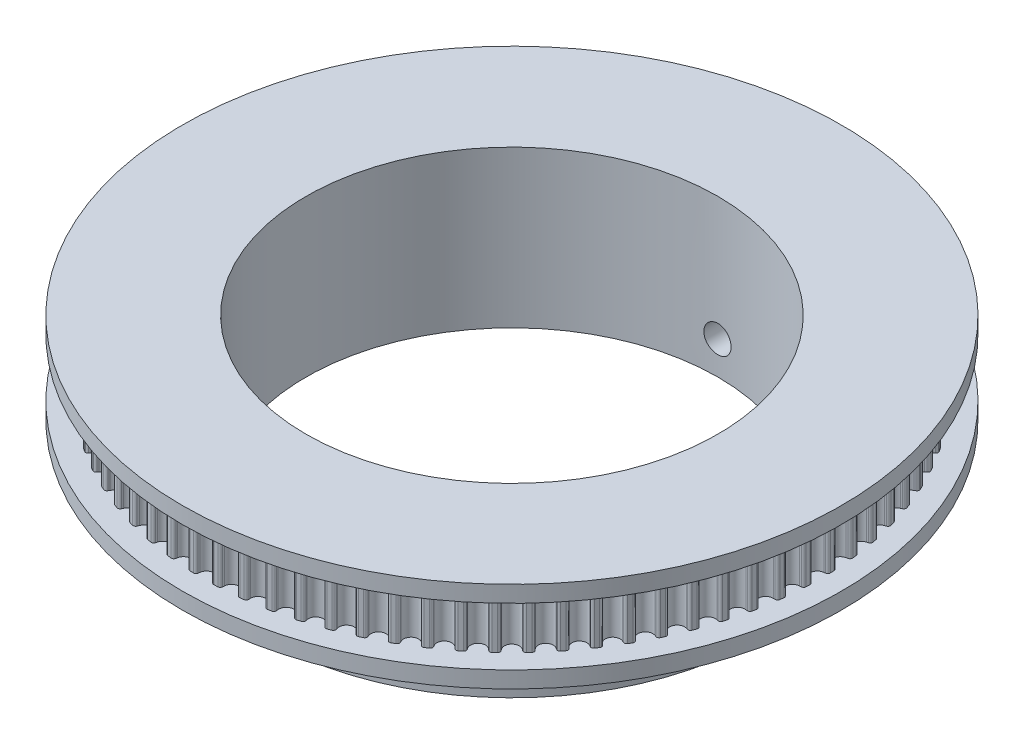
SolidWorks part; units mm, degrees
material "6061 合金"
ref_plane "前视基准面" through (0, 0, 0) normal (0, 0, 1) x (1, 0, 0)
ref_plane "上视基准面" through (0, 0, 0) normal (0, 1, 0) x (1, 0, 0)
ref_plane "右视基准面" through (0, 0, 0) normal (1, 0, 0) x (0, 0, -1)
sketch "草图1" plane through (0, 0, 0) normal (0, 1, 0) x (1, 0, 0)
  circle A0 centre (0, 0) radius 40
  dimension "D1" = 80
extrude "凸台-拉伸1" add sketch "草图1" along normal mid plane 11
sketch "草图2" plane through (0, 0, 0) normal (0, 1, 0) x (1, 0, 0)
  line L0 (0, 0) -> (0, 37.815) construction
  line L1 (-0.9274, 37.1503) -> (-0.9032, 36.9531)
  line L2 (0.9274, 37.1503) -> (0.9032, 36.9531)
  line L3 (-0.95, 37.2332) -> (0.95, 37.2332) construction
  line L4 (1.9902, 37.1086) -> (1.9989, 36.9101)
  line L5 (3.8394, 36.9631) -> (3.7997, 36.7683)
  line L6 (4.8956, 36.838) -> (4.8886, 36.6394)
  line L7 (6.7276, 36.5479) -> (6.6728, 36.3569)
  line L8 (7.7708, 36.3404) -> (7.7483, 36.1429)
  line L9 (9.5744, 35.9074) -> (9.5048, 35.7212)
  line L10 (10.598, 35.6187) -> (10.5601, 35.4236)
  line L11 (12.3621, 35.0455) -> (12.2781, 34.8654)
  line L12 (13.36, 34.6774) -> (13.3069, 34.4859)
  line L13 (15.0737, 33.9675) -> (14.9758, 33.7946)
  line L14 (16.0396, 33.5222) -> (15.9716, 33.3355)
  line L15 (17.6923, 32.6802) -> (17.5811, 32.5154)
  line L16 (18.6202, 32.1605) -> (18.5378, 31.9796)
  line L17 (20.2018, 31.1913) -> (20.0781, 31.0358)
  line L18 (21.0861, 30.6004) -> (20.9898, 30.4266)
  line L19 (22.5867, 29.5101) -> (22.4512, 29.3648)
  line L20 (23.422, 28.8517) -> (23.3123, 28.6859)
  line L21 (24.8324, 27.647) -> (24.6859, 27.5128)
  line L22 (25.6135, 26.9251) -> (25.4911, 26.7685)
  line L23 (26.9251, 25.6135) -> (26.7685, 25.4911)
  line L24 (27.647, 24.8324) -> (27.5128, 24.6859)
  line L25 (28.8517, 23.422) -> (28.6859, 23.3123)
  line L26 (29.5101, 22.5867) -> (29.3648, 22.4512)
  line L27 (30.6004, 21.0861) -> (30.4266, 20.9898)
  line L28 (31.1913, 20.2018) -> (31.0358, 20.0781)
  line L29 (32.1605, 18.6202) -> (31.9796, 18.5378)
  line L30 (32.6802, 17.6923) -> (32.5154, 17.5811)
  line L31 (33.5222, 16.0396) -> (33.3355, 15.9716)
  line L32 (33.9675, 15.0737) -> (33.7946, 14.9758)
  line L33 (34.6774, 13.36) -> (34.4859, 13.3069)
  line L34 (35.0455, 12.3621) -> (34.8654, 12.2781)
  line L35 (35.6187, 10.598) -> (35.4236, 10.5601)
  line L36 (35.9074, 9.5744) -> (35.7212, 9.5048)
  line L37 (36.3404, 7.7708) -> (36.1429, 7.7483)
  line L38 (36.5479, 6.7276) -> (36.3569, 6.6728)
  line L39 (36.838, 4.8956) -> (36.6394, 4.8886)
  line L40 (36.9631, 3.8394) -> (36.7683, 3.7997)
  line L41 (37.1086, 1.9902) -> (36.9101, 1.9989)
  line L42 (37.1503, 0.9274) -> (36.9531, 0.9032)
  line L43 (37.1503, -0.9274) -> (36.9531, -0.9032)
  line L44 (37.1086, -1.9902) -> (36.9101, -1.9989)
  line L45 (36.9631, -3.8394) -> (36.7683, -3.7997)
  line L46 (36.838, -4.8956) -> (36.6394, -4.8886)
  line L47 (36.5479, -6.7276) -> (36.3569, -6.6728)
  line L48 (36.3404, -7.7708) -> (36.1429, -7.7483)
  line L49 (35.9074, -9.5744) -> (35.7212, -9.5048)
  line L50 (35.6187, -10.598) -> (35.4236, -10.5601)
  line L51 (35.0455, -12.3621) -> (34.8654, -12.2781)
  line L52 (34.6774, -13.36) -> (34.4859, -13.3069)
  line L53 (33.9675, -15.0737) -> (33.7946, -14.9758)
  line L54 (33.5222, -16.0396) -> (33.3355, -15.9716)
  line L55 (32.6802, -17.6923) -> (32.5154, -17.5811)
  line L56 (32.1605, -18.6202) -> (31.9796, -18.5378)
  line L57 (31.1913, -20.2018) -> (31.0358, -20.0781)
  line L58 (30.6004, -21.0861) -> (30.4266, -20.9898)
  line L59 (29.5101, -22.5867) -> (29.3648, -22.4512)
  line L60 (28.8517, -23.422) -> (28.6859, -23.3123)
  line L61 (27.647, -24.8324) -> (27.5128, -24.6859)
  line L62 (26.9251, -25.6135) -> (26.7685, -25.4911)
  line L63 (25.6135, -26.9251) -> (25.4911, -26.7685)
  line L64 (24.8324, -27.647) -> (24.6859, -27.5128)
  line L65 (23.422, -28.8517) -> (23.3123, -28.6859)
  line L66 (22.5867, -29.5101) -> (22.4512, -29.3648)
  line L67 (21.0861, -30.6004) -> (20.9898, -30.4266)
  line L68 (20.2018, -31.1913) -> (20.0781, -31.0358)
  line L69 (18.6202, -32.1605) -> (18.5378, -31.9796)
  line L70 (17.6923, -32.6802) -> (17.5811, -32.5154)
  line L71 (16.0396, -33.5222) -> (15.9716, -33.3355)
  line L72 (15.0737, -33.9675) -> (14.9758, -33.7946)
  line L73 (13.36, -34.6774) -> (13.3069, -34.4859)
  line L74 (12.3621, -35.0455) -> (12.2781, -34.8654)
  line L75 (10.598, -35.6187) -> (10.5601, -35.4236)
  line L76 (9.5744, -35.9074) -> (9.5048, -35.7212)
  line L77 (7.7708, -36.3404) -> (7.7483, -36.1429)
  line L78 (6.7276, -36.5479) -> (6.6728, -36.3569)
  line L79 (4.8956, -36.838) -> (4.8886, -36.6394)
  line L80 (3.8394, -36.9631) -> (3.7997, -36.7683)
  line L81 (1.9902, -37.1086) -> (1.9989, -36.9101)
  line L82 (0.9274, -37.1503) -> (0.9032, -36.9531)
  line L83 (-0.9274, -37.1503) -> (-0.9032, -36.9531)
  line L84 (-1.9902, -37.1086) -> (-1.9989, -36.9101)
  line L85 (-3.8394, -36.9631) -> (-3.7997, -36.7683)
  line L86 (-4.8956, -36.838) -> (-4.8886, -36.6394)
  line L87 (-6.7276, -36.5479) -> (-6.6728, -36.3569)
  line L88 (-7.7708, -36.3404) -> (-7.7483, -36.1429)
  line L89 (-9.5744, -35.9074) -> (-9.5048, -35.7212)
  line L90 (-10.598, -35.6187) -> (-10.5601, -35.4236)
  line L91 (-12.3621, -35.0455) -> (-12.2781, -34.8654)
  line L92 (-13.36, -34.6774) -> (-13.3069, -34.4859)
  line L93 (-15.0737, -33.9675) -> (-14.9758, -33.7946)
  line L94 (-16.0396, -33.5222) -> (-15.9716, -33.3355)
  line L95 (-17.6923, -32.6802) -> (-17.5811, -32.5154)
  line L96 (-18.6202, -32.1605) -> (-18.5378, -31.9796)
  line L97 (-20.2018, -31.1913) -> (-20.0781, -31.0358)
  line L98 (-21.0861, -30.6004) -> (-20.9898, -30.4266)
  line L99 (-22.5867, -29.5101) -> (-22.4512, -29.3648)
  line L100 (-23.422, -28.8517) -> (-23.3123, -28.6859)
  line L101 (-24.8324, -27.647) -> (-24.6859, -27.5128)
  line L102 (-25.6135, -26.9251) -> (-25.4911, -26.7685)
  line L103 (-26.9251, -25.6135) -> (-26.7685, -25.4911)
  line L104 (-27.647, -24.8324) -> (-27.5128, -24.6859)
  line L105 (-28.8517, -23.422) -> (-28.6859, -23.3123)
  line L106 (-29.5101, -22.5867) -> (-29.3648, -22.4512)
  line L107 (-30.6004, -21.0861) -> (-30.4266, -20.9898)
  line L108 (-31.1913, -20.2018) -> (-31.0358, -20.0781)
  line L109 (-32.1605, -18.6202) -> (-31.9796, -18.5378)
  line L110 (-32.6802, -17.6923) -> (-32.5154, -17.5811)
  line L111 (-33.5222, -16.0396) -> (-33.3355, -15.9716)
  line L112 (-33.9675, -15.0737) -> (-33.7946, -14.9758)
  line L113 (-34.6774, -13.36) -> (-34.4859, -13.3069)
  line L114 (-35.0455, -12.3621) -> (-34.8654, -12.2781)
  line L115 (-35.6187, -10.598) -> (-35.4236, -10.5601)
  line L116 (-35.9074, -9.5744) -> (-35.7212, -9.5048)
  line L117 (-36.3404, -7.7708) -> (-36.1429, -7.7483)
  line L118 (-36.5479, -6.7276) -> (-36.3569, -6.6728)
  line L119 (-36.838, -4.8956) -> (-36.6394, -4.8886)
  line L120 (-36.9631, -3.8394) -> (-36.7683, -3.7997)
  line L121 (-37.1086, -1.9902) -> (-36.9101, -1.9989)
  line L122 (-37.1503, -0.9274) -> (-36.9531, -0.9032)
  line L123 (-37.1503, 0.9274) -> (-36.9531, 0.9032)
  line L124 (-37.1086, 1.9902) -> (-36.9101, 1.9989)
  line L125 (-36.9631, 3.8394) -> (-36.7683, 3.7997)
  line L126 (-36.838, 4.8956) -> (-36.6394, 4.8886)
  line L127 (-36.5479, 6.7276) -> (-36.3569, 6.6728)
  line L128 (-36.3404, 7.7708) -> (-36.1429, 7.7483)
  line L129 (-35.9074, 9.5744) -> (-35.7212, 9.5048)
  line L130 (-35.6187, 10.598) -> (-35.4236, 10.5601)
  line L131 (-35.0455, 12.3621) -> (-34.8654, 12.2781)
  line L132 (-34.6774, 13.36) -> (-34.4859, 13.3069)
  line L133 (-33.9675, 15.0737) -> (-33.7946, 14.9758)
  line L134 (-33.5222, 16.0396) -> (-33.3355, 15.9716)
  line L135 (-32.6802, 17.6923) -> (-32.5154, 17.5811)
  line L136 (-32.1605, 18.6202) -> (-31.9796, 18.5378)
  line L137 (-31.1913, 20.2018) -> (-31.0358, 20.0781)
  line L138 (-30.6004, 21.0861) -> (-30.4266, 20.9898)
  line L139 (-29.5101, 22.5867) -> (-29.3648, 22.4512)
  line L140 (-28.8517, 23.422) -> (-28.6859, 23.3123)
  line L141 (-27.647, 24.8324) -> (-27.5128, 24.6859)
  line L142 (-26.9251, 25.6135) -> (-26.7685, 25.4911)
  line L143 (-25.6135, 26.9251) -> (-25.4911, 26.7685)
  line L144 (-24.8324, 27.647) -> (-24.6859, 27.5128)
  line L145 (-23.422, 28.8517) -> (-23.3123, 28.6859)
  line L146 (-22.5867, 29.5101) -> (-22.4512, 29.3648)
  line L147 (-21.0861, 30.6004) -> (-20.9898, 30.4266)
  line L148 (-20.2018, 31.1913) -> (-20.0781, 31.0358)
  line L149 (-18.6202, 32.1605) -> (-18.5378, 31.9796)
  line L150 (-17.6923, 32.6802) -> (-17.5811, 32.5154)
  line L151 (-16.0396, 33.5222) -> (-15.9716, 33.3355)
  line L152 (-15.0737, 33.9675) -> (-14.9758, 33.7946)
  line L153 (-13.36, 34.6774) -> (-13.3069, 34.4859)
  line L154 (-12.3621, 35.0455) -> (-12.2781, 34.8654)
  line L155 (-10.598, 35.6187) -> (-10.5601, 35.4236)
  line L156 (-9.5744, 35.9074) -> (-9.5048, 35.7212)
  line L157 (-7.7708, 36.3404) -> (-7.7483, 36.1429)
  line L158 (-6.7276, 36.5479) -> (-6.6728, 36.3569)
  line L159 (-4.8956, 36.838) -> (-4.8886, 36.6394)
  line L160 (-3.8394, 36.9631) -> (-3.7997, 36.7683)
  line L161 (-1.9902, 37.1086) -> (-1.9989, 36.9101)
  arc A0 (-1.2351, 37.4136) -> (-1.7041, 37.3952) centre (0, 0) ccw
  arc A1 (1.7041, 37.3952) -> (1.2351, 37.4136) centre (0, 0) ccw
  arc A3 (-0.9032, 36.9531) -> (0.9032, 36.9531) centre (0, 37.064) ccw
  arc A4 (-0.9274, 37.1503) -> (-1.2351, 37.4136) centre (-1.2252, 37.1138) ccw
  arc A5 (0.9274, 37.1503) -> (1.2351, 37.4136) centre (1.2252, 37.1138) cw
  arc A6 (1.9902, 37.1086) -> (1.7041, 37.3952) centre (1.6905, 37.0955) ccw
  arc A7 (1.9989, 36.9101) -> (3.7997, 36.7683) centre (2.908, 36.9497) ccw
  arc A8 (3.8394, 36.9631) -> (4.1667, 37.2014) centre (4.1333, 36.9032) cw
  arc A9 (4.6329, 37.1462) -> (4.1667, 37.2014) centre (0, 0) ccw
  arc A10 (4.8956, 36.838) -> (4.6329, 37.1462) centre (4.5958, 36.8485) ccw
  arc A11 (4.8886, 36.6394) -> (6.6728, 36.3569) centre (5.7981, 36.6077) ccw
  arc A12 (6.7276, 36.5479) -> (7.0727, 36.7598) centre (7.016, 36.4652) cw
  arc A13 (7.5331, 36.6682) -> (7.0727, 36.7598) centre (0, 0) ccw
  arc A14 (7.7708, 36.3404) -> (7.5331, 36.6682) centre (7.4727, 36.3743) ccw
  arc A15 (7.7483, 36.1429) -> (9.5048, 35.7212) centre (8.6524, 36.0399) ccw
  arc A16 (9.5744, 35.9074) -> (9.935, 36.0915) centre (9.8554, 35.8023) cw
  arc A17 (10.3868, 35.9641) -> (9.935, 36.0915) centre (0, 0) ccw
  arc A18 (10.598, 35.6187) -> (10.3868, 35.9641) centre (10.3036, 35.6759) ccw
  arc A19 (10.5601, 35.4236) -> (12.2781, 34.8654) centre (11.4534, 35.25) ccw
  arc A20 (12.3621, 35.0455) -> (12.7361, 35.2008) centre (12.634, 34.9187) cw
  arc A21 (13.1765, 35.0383) -> (12.7361, 35.2008) centre (0, 0) ccw
  arc A22 (13.36, 34.6774) -> (13.1765, 35.0383) centre (13.0709, 34.7575) ccw
  arc A23 (13.3069, 34.4859) -> (14.9758, 33.7946) centre (14.1838, 34.2427) ccw
  arc A24 (15.0737, 33.9675) -> (15.4587, 34.093) centre (15.3348, 33.8198) cw
  arc A25 (15.8849, 33.8965) -> (15.4587, 34.093) centre (0, 0) ccw
  arc A26 (16.0396, 33.5222) -> (15.8849, 33.8965) centre (15.7576, 33.6249) ccw
  arc A27 (15.9716, 33.3355) -> (17.5811, 32.5154) centre (16.8267, 33.0243) ccw
  arc A28 (17.6923, 32.6802) -> (18.0859, 32.7751) centre (17.941, 32.5124) cw
  arc A29 (18.4955, 32.5457) -> (18.0859, 32.7751) centre (0, 0) ccw
  arc A30 (18.6202, 32.1605) -> (18.4955, 32.5457) centre (18.3472, 32.2849) ccw
  arc A31 (18.5378, 31.9796) -> (20.0781, 31.0358) centre (19.3659, 31.6023) ccw
  arc A32 (20.2018, 31.1913) -> (20.6017, 31.255) centre (20.4366, 31.0045) cw
  arc A33 (20.992, 30.9942) -> (20.6017, 31.255) centre (0, 0) ccw
  arc A34 (21.0861, 30.6004) -> (20.992, 30.9942) centre (20.8237, 30.7458) ccw
  arc A35 (20.9898, 30.4266) -> (22.4512, 29.3648) centre (21.7857, 29.9854) ccw
  arc A36 (22.5867, 29.5101) -> (22.9904, 29.5423) centre (22.8061, 29.3055) cw
  arc A37 (23.359, 29.2517) -> (22.9904, 29.5423) centre (0, 0) ccw
  arc A38 (23.422, 28.8517) -> (23.359, 29.2517) centre (23.1718, 29.0172) ccw
  arc A39 (23.3123, 28.6859) -> (24.6859, 27.5128) centre (24.0711, 28.1837) ccw
  arc A40 (24.8324, 27.647) -> (25.2374, 27.6474) centre (25.0351, 27.4258) cw
  arc A41 (25.5821, 27.3288) -> (25.2374, 27.6474) centre (0, 0) ccw
  arc A42 (25.6135, 26.9251) -> (25.5821, 27.3288) centre (25.3771, 27.1098) ccw
  arc A43 (25.4911, 26.7685) -> (26.7685, 25.4911) centre (26.2082, 26.2082) ccw
  arc A44 (26.9251, 25.6135) -> (27.3288, 25.5821) centre (27.1098, 25.3771) cw
  arc A45 (27.6474, 25.2374) -> (27.3288, 25.5821) centre (0, 0) ccw
  arc A46 (27.647, 24.8324) -> (27.6474, 25.2374) centre (27.4258, 25.0351) ccw
  arc A47 (27.5128, 24.6859) -> (28.6859, 23.3123) centre (28.1837, 24.0711) ccw
  arc A48 (28.8517, 23.422) -> (29.2517, 23.359) centre (29.0172, 23.1718) cw
  arc A49 (29.5423, 22.9904) -> (29.2517, 23.359) centre (0, 0) ccw
  arc A50 (29.5101, 22.5867) -> (29.5423, 22.9904) centre (29.3055, 22.8061) ccw
  arc A51 (29.3648, 22.4512) -> (30.4266, 20.9898) centre (29.9854, 21.7857) ccw
  arc A52 (30.6004, 21.0861) -> (30.9942, 20.992) centre (30.7458, 20.8237) cw
  arc A53 (31.255, 20.6017) -> (30.9942, 20.992) centre (0, 0) ccw
  arc A54 (31.1913, 20.2018) -> (31.255, 20.6017) centre (31.0045, 20.4366) ccw
  arc A55 (31.0358, 20.0781) -> (31.9796, 18.5378) centre (31.6023, 19.3659) ccw
  arc A56 (32.1605, 18.6202) -> (32.5457, 18.4955) centre (32.2849, 18.3472) cw
  arc A57 (32.7751, 18.0859) -> (32.5457, 18.4955) centre (0, 0) ccw
  arc A58 (32.6802, 17.6923) -> (32.7751, 18.0859) centre (32.5124, 17.941) ccw
  arc A59 (32.5154, 17.5811) -> (33.3355, 15.9716) centre (33.0243, 16.8267) ccw
  arc A60 (33.5222, 16.0396) -> (33.8965, 15.8849) centre (33.6249, 15.7576) cw
  arc A61 (34.093, 15.4587) -> (33.8965, 15.8849) centre (0, 0) ccw
  arc A62 (33.9675, 15.0737) -> (34.093, 15.4587) centre (33.8198, 15.3348) ccw
  arc A63 (33.7946, 14.9758) -> (34.4859, 13.3069) centre (34.2427, 14.1838) ccw
  arc A64 (34.6774, 13.36) -> (35.0383, 13.1765) centre (34.7575, 13.0709) cw
  arc A65 (35.2008, 12.7361) -> (35.0383, 13.1765) centre (0, 0) ccw
  arc A66 (35.0455, 12.3621) -> (35.2008, 12.7361) centre (34.9187, 12.634) ccw
  arc A67 (34.8654, 12.2781) -> (35.4236, 10.5601) centre (35.25, 11.4534) ccw
  arc A68 (35.6187, 10.598) -> (35.9641, 10.3868) centre (35.6759, 10.3036) cw
  arc A69 (36.0915, 9.935) -> (35.9641, 10.3868) centre (0, 0) ccw
  arc A70 (35.9074, 9.5744) -> (36.0915, 9.935) centre (35.8023, 9.8554) ccw
  arc A71 (35.7212, 9.5048) -> (36.1429, 7.7483) centre (36.0399, 8.6524) ccw
  arc A72 (36.3404, 7.7708) -> (36.6682, 7.5331) centre (36.3743, 7.4727) cw
  arc A73 (36.7598, 7.0727) -> (36.6682, 7.5331) centre (0, 0) ccw
  arc A74 (36.5479, 6.7276) -> (36.7598, 7.0727) centre (36.4652, 7.016) ccw
  arc A75 (36.3569, 6.6728) -> (36.6394, 4.8886) centre (36.6077, 5.7981) ccw
  arc A76 (36.838, 4.8956) -> (37.1462, 4.6329) centre (36.8485, 4.5958) cw
  arc A77 (37.2014, 4.1667) -> (37.1462, 4.6329) centre (0, 0) ccw
  arc A78 (36.9631, 3.8394) -> (37.2014, 4.1667) centre (36.9032, 4.1333) ccw
  arc A79 (36.7683, 3.7997) -> (36.9101, 1.9989) centre (36.9497, 2.908) ccw
  arc A80 (37.1086, 1.9902) -> (37.3952, 1.7041) centre (37.0955, 1.6905) cw
  arc A81 (37.4136, 1.2351) -> (37.3952, 1.7041) centre (0, 0) ccw
  arc A82 (37.1503, 0.9274) -> (37.4136, 1.2351) centre (37.1138, 1.2252) ccw
  arc A83 (36.9531, 0.9032) -> (36.9531, -0.9032) centre (37.064, 0) ccw
  arc A84 (37.1503, -0.9274) -> (37.4136, -1.2351) centre (37.1138, -1.2252) cw
  arc A85 (37.3952, -1.7041) -> (37.4136, -1.2351) centre (0, 0) ccw
  arc A86 (37.1086, -1.9902) -> (37.3952, -1.7041) centre (37.0955, -1.6905) ccw
  arc A87 (36.9101, -1.9989) -> (36.7683, -3.7997) centre (36.9497, -2.908) ccw
  arc A88 (36.9631, -3.8394) -> (37.2014, -4.1667) centre (36.9032, -4.1333) cw
  arc A89 (37.1462, -4.6329) -> (37.2014, -4.1667) centre (0, 0) ccw
  arc A90 (36.838, -4.8956) -> (37.1462, -4.6329) centre (36.8485, -4.5958) ccw
  arc A91 (36.6394, -4.8886) -> (36.3569, -6.6728) centre (36.6077, -5.7981) ccw
  arc A92 (36.5479, -6.7276) -> (36.7598, -7.0727) centre (36.4652, -7.016) cw
  arc A93 (36.6682, -7.5331) -> (36.7598, -7.0727) centre (0, 0) ccw
  arc A94 (36.3404, -7.7708) -> (36.6682, -7.5331) centre (36.3743, -7.4727) ccw
  arc A95 (36.1429, -7.7483) -> (35.7212, -9.5048) centre (36.0399, -8.6524) ccw
  arc A96 (35.9074, -9.5744) -> (36.0915, -9.935) centre (35.8023, -9.8554) cw
  arc A97 (35.9641, -10.3868) -> (36.0915, -9.935) centre (0, 0) ccw
  arc A98 (35.6187, -10.598) -> (35.9641, -10.3868) centre (35.6759, -10.3036) ccw
  arc A99 (35.4236, -10.5601) -> (34.8654, -12.2781) centre (35.25, -11.4534) ccw
  arc A100 (35.0455, -12.3621) -> (35.2008, -12.7361) centre (34.9187, -12.634) cw
  arc A101 (35.0383, -13.1765) -> (35.2008, -12.7361) centre (0, 0) ccw
  arc A102 (34.6774, -13.36) -> (35.0383, -13.1765) centre (34.7575, -13.0709) ccw
  arc A103 (34.4859, -13.3069) -> (33.7946, -14.9758) centre (34.2427, -14.1838) ccw
  arc A104 (33.9675, -15.0737) -> (34.093, -15.4587) centre (33.8198, -15.3348) cw
  arc A105 (33.8965, -15.8849) -> (34.093, -15.4587) centre (0, 0) ccw
  arc A106 (33.5222, -16.0396) -> (33.8965, -15.8849) centre (33.6249, -15.7576) ccw
  arc A107 (33.3355, -15.9716) -> (32.5154, -17.5811) centre (33.0243, -16.8267) ccw
  arc A108 (32.6802, -17.6923) -> (32.7751, -18.0859) centre (32.5124, -17.941) cw
  arc A109 (32.5457, -18.4955) -> (32.7751, -18.0859) centre (0, 0) ccw
  arc A110 (32.1605, -18.6202) -> (32.5457, -18.4955) centre (32.2849, -18.3472) ccw
  arc A111 (31.9796, -18.5378) -> (31.0358, -20.0781) centre (31.6023, -19.3659) ccw
  arc A112 (31.1913, -20.2018) -> (31.255, -20.6017) centre (31.0045, -20.4366) cw
  arc A113 (30.9942, -20.992) -> (31.255, -20.6017) centre (0, 0) ccw
  arc A114 (30.6004, -21.0861) -> (30.9942, -20.992) centre (30.7458, -20.8237) ccw
  arc A115 (30.4266, -20.9898) -> (29.3648, -22.4512) centre (29.9854, -21.7857) ccw
  arc A116 (29.5101, -22.5867) -> (29.5423, -22.9904) centre (29.3055, -22.8061) cw
  arc A117 (29.2517, -23.359) -> (29.5423, -22.9904) centre (0, 0) ccw
  arc A118 (28.8517, -23.422) -> (29.2517, -23.359) centre (29.0172, -23.1718) ccw
  arc A119 (28.6859, -23.3123) -> (27.5128, -24.6859) centre (28.1837, -24.0711) ccw
  arc A120 (27.647, -24.8324) -> (27.6474, -25.2374) centre (27.4258, -25.0351) cw
  arc A121 (27.3288, -25.5821) -> (27.6474, -25.2374) centre (0, 0) ccw
  arc A122 (26.9251, -25.6135) -> (27.3288, -25.5821) centre (27.1098, -25.3771) ccw
  arc A123 (26.7685, -25.4911) -> (25.4911, -26.7685) centre (26.2082, -26.2082) ccw
  arc A124 (25.6135, -26.9251) -> (25.5821, -27.3288) centre (25.3771, -27.1098) cw
  arc A125 (25.2374, -27.6474) -> (25.5821, -27.3288) centre (0, 0) ccw
  arc A126 (24.8324, -27.647) -> (25.2374, -27.6474) centre (25.0351, -27.4258) ccw
  arc A127 (24.6859, -27.5128) -> (23.3123, -28.6859) centre (24.0711, -28.1837) ccw
  arc A128 (23.422, -28.8517) -> (23.359, -29.2517) centre (23.1718, -29.0172) cw
  arc A129 (22.9904, -29.5423) -> (23.359, -29.2517) centre (0, 0) ccw
  arc A130 (22.5867, -29.5101) -> (22.9904, -29.5423) centre (22.8061, -29.3055) ccw
  arc A131 (22.4512, -29.3648) -> (20.9898, -30.4266) centre (21.7857, -29.9854) ccw
  arc A132 (21.0861, -30.6004) -> (20.992, -30.9942) centre (20.8237, -30.7458) cw
  arc A133 (20.6017, -31.255) -> (20.992, -30.9942) centre (0, 0) ccw
  arc A134 (20.2018, -31.1913) -> (20.6017, -31.255) centre (20.4366, -31.0045) ccw
  arc A135 (20.0781, -31.0358) -> (18.5378, -31.9796) centre (19.3659, -31.6023) ccw
  arc A136 (18.6202, -32.1605) -> (18.4955, -32.5457) centre (18.3472, -32.2849) cw
  arc A137 (18.0859, -32.7751) -> (18.4955, -32.5457) centre (0, 0) ccw
  arc A138 (17.6923, -32.6802) -> (18.0859, -32.7751) centre (17.941, -32.5124) ccw
  arc A139 (17.5811, -32.5154) -> (15.9716, -33.3355) centre (16.8267, -33.0243) ccw
  arc A140 (16.0396, -33.5222) -> (15.8849, -33.8965) centre (15.7576, -33.6249) cw
  arc A141 (15.4587, -34.093) -> (15.8849, -33.8965) centre (0, 0) ccw
  arc A142 (15.0737, -33.9675) -> (15.4587, -34.093) centre (15.3348, -33.8198) ccw
  arc A143 (14.9758, -33.7946) -> (13.3069, -34.4859) centre (14.1838, -34.2427) ccw
  arc A144 (13.36, -34.6774) -> (13.1765, -35.0383) centre (13.0709, -34.7575) cw
  arc A145 (12.7361, -35.2008) -> (13.1765, -35.0383) centre (0, 0) ccw
  arc A146 (12.3621, -35.0455) -> (12.7361, -35.2008) centre (12.634, -34.9187) ccw
  arc A147 (12.2781, -34.8654) -> (10.5601, -35.4236) centre (11.4534, -35.25) ccw
  arc A148 (10.598, -35.6187) -> (10.3868, -35.9641) centre (10.3036, -35.6759) cw
  arc A149 (9.935, -36.0915) -> (10.3868, -35.9641) centre (0, 0) ccw
  arc A150 (9.5744, -35.9074) -> (9.935, -36.0915) centre (9.8554, -35.8023) ccw
  arc A151 (9.5048, -35.7212) -> (7.7483, -36.1429) centre (8.6524, -36.0399) ccw
  arc A152 (7.7708, -36.3404) -> (7.5331, -36.6682) centre (7.4727, -36.3743) cw
  arc A153 (7.0727, -36.7598) -> (7.5331, -36.6682) centre (0, 0) ccw
  arc A154 (6.7276, -36.5479) -> (7.0727, -36.7598) centre (7.016, -36.4652) ccw
  arc A155 (6.6728, -36.3569) -> (4.8886, -36.6394) centre (5.7981, -36.6077) ccw
  arc A156 (4.8956, -36.838) -> (4.6329, -37.1462) centre (4.5958, -36.8485) cw
  arc A157 (4.1667, -37.2014) -> (4.6329, -37.1462) centre (0, 0) ccw
  arc A158 (3.8394, -36.9631) -> (4.1667, -37.2014) centre (4.1333, -36.9032) ccw
  arc A159 (3.7997, -36.7683) -> (1.9989, -36.9101) centre (2.908, -36.9497) ccw
  arc A160 (1.9902, -37.1086) -> (1.7041, -37.3952) centre (1.6905, -37.0955) cw
  arc A161 (1.2351, -37.4136) -> (1.7041, -37.3952) centre (0, 0) ccw
  arc A162 (0.9274, -37.1503) -> (1.2351, -37.4136) centre (1.2252, -37.1138) ccw
  arc A163 (0.9032, -36.9531) -> (-0.9032, -36.9531) centre (0, -37.064) ccw
  arc A164 (-0.9274, -37.1503) -> (-1.2351, -37.4136) centre (-1.2252, -37.1138) cw
  arc A165 (-1.7041, -37.3952) -> (-1.2351, -37.4136) centre (0, 0) ccw
  arc A166 (-1.9902, -37.1086) -> (-1.7041, -37.3952) centre (-1.6905, -37.0955) ccw
  arc A167 (-1.9989, -36.9101) -> (-3.7997, -36.7683) centre (-2.908, -36.9497) ccw
  arc A168 (-3.8394, -36.9631) -> (-4.1667, -37.2014) centre (-4.1333, -36.9032) cw
  arc A169 (-4.6329, -37.1462) -> (-4.1667, -37.2014) centre (0, 0) ccw
  arc A170 (-4.8956, -36.838) -> (-4.6329, -37.1462) centre (-4.5958, -36.8485) ccw
  arc A171 (-4.8886, -36.6394) -> (-6.6728, -36.3569) centre (-5.7981, -36.6077) ccw
  arc A172 (-6.7276, -36.5479) -> (-7.0727, -36.7598) centre (-7.016, -36.4652) cw
  arc A173 (-7.5331, -36.6682) -> (-7.0727, -36.7598) centre (0, 0) ccw
  arc A174 (-7.7708, -36.3404) -> (-7.5331, -36.6682) centre (-7.4727, -36.3743) ccw
  arc A175 (-7.7483, -36.1429) -> (-9.5048, -35.7212) centre (-8.6524, -36.0399) ccw
  arc A176 (-9.5744, -35.9074) -> (-9.935, -36.0915) centre (-9.8554, -35.8023) cw
  arc A177 (-10.3868, -35.9641) -> (-9.935, -36.0915) centre (0, 0) ccw
  arc A178 (-10.598, -35.6187) -> (-10.3868, -35.9641) centre (-10.3036, -35.6759) ccw
  arc A179 (-10.5601, -35.4236) -> (-12.2781, -34.8654) centre (-11.4534, -35.25) ccw
  arc A180 (-12.3621, -35.0455) -> (-12.7361, -35.2008) centre (-12.634, -34.9187) cw
  arc A181 (-13.1765, -35.0383) -> (-12.7361, -35.2008) centre (0, 0) ccw
  arc A182 (-13.36, -34.6774) -> (-13.1765, -35.0383) centre (-13.0709, -34.7575) ccw
  arc A183 (-13.3069, -34.4859) -> (-14.9758, -33.7946) centre (-14.1838, -34.2427) ccw
  arc A184 (-15.0737, -33.9675) -> (-15.4587, -34.093) centre (-15.3348, -33.8198) cw
  arc A185 (-15.8849, -33.8965) -> (-15.4587, -34.093) centre (0, 0) ccw
  arc A186 (-16.0396, -33.5222) -> (-15.8849, -33.8965) centre (-15.7576, -33.6249) ccw
  arc A187 (-15.9716, -33.3355) -> (-17.5811, -32.5154) centre (-16.8267, -33.0243) ccw
  arc A188 (-17.6923, -32.6802) -> (-18.0859, -32.7751) centre (-17.941, -32.5124) cw
  arc A189 (-18.4955, -32.5457) -> (-18.0859, -32.7751) centre (0, 0) ccw
  arc A190 (-18.6202, -32.1605) -> (-18.4955, -32.5457) centre (-18.3472, -32.2849) ccw
  arc A191 (-18.5378, -31.9796) -> (-20.0781, -31.0358) centre (-19.3659, -31.6023) ccw
  arc A192 (-20.2018, -31.1913) -> (-20.6017, -31.255) centre (-20.4366, -31.0045) cw
  arc A193 (-20.992, -30.9942) -> (-20.6017, -31.255) centre (0, 0) ccw
  arc A194 (-21.0861, -30.6004) -> (-20.992, -30.9942) centre (-20.8237, -30.7458) ccw
  arc A195 (-20.9898, -30.4266) -> (-22.4512, -29.3648) centre (-21.7857, -29.9854) ccw
  arc A196 (-22.5867, -29.5101) -> (-22.9904, -29.5423) centre (-22.8061, -29.3055) cw
  arc A197 (-23.359, -29.2517) -> (-22.9904, -29.5423) centre (0, 0) ccw
  arc A198 (-23.422, -28.8517) -> (-23.359, -29.2517) centre (-23.1718, -29.0172) ccw
  arc A199 (-23.3123, -28.6859) -> (-24.6859, -27.5128) centre (-24.0711, -28.1837) ccw
  arc A200 (-24.8324, -27.647) -> (-25.2374, -27.6474) centre (-25.0351, -27.4258) cw
  arc A201 (-25.5821, -27.3288) -> (-25.2374, -27.6474) centre (0, 0) ccw
  arc A202 (-25.6135, -26.9251) -> (-25.5821, -27.3288) centre (-25.3771, -27.1098) ccw
  arc A203 (-25.4911, -26.7685) -> (-26.7685, -25.4911) centre (-26.2082, -26.2082) ccw
  arc A204 (-26.9251, -25.6135) -> (-27.3288, -25.5821) centre (-27.1098, -25.3771) cw
  arc A205 (-27.6474, -25.2374) -> (-27.3288, -25.5821) centre (0, 0) ccw
  arc A206 (-27.647, -24.8324) -> (-27.6474, -25.2374) centre (-27.4258, -25.0351) ccw
  arc A207 (-27.5128, -24.6859) -> (-28.6859, -23.3123) centre (-28.1837, -24.0711) ccw
  arc A208 (-28.8517, -23.422) -> (-29.2517, -23.359) centre (-29.0172, -23.1718) cw
  arc A209 (-29.5423, -22.9904) -> (-29.2517, -23.359) centre (0, 0) ccw
  arc A210 (-29.5101, -22.5867) -> (-29.5423, -22.9904) centre (-29.3055, -22.8061) ccw
  arc A211 (-29.3648, -22.4512) -> (-30.4266, -20.9898) centre (-29.9854, -21.7857) ccw
  arc A212 (-30.6004, -21.0861) -> (-30.9942, -20.992) centre (-30.7458, -20.8237) cw
  arc A213 (-31.255, -20.6017) -> (-30.9942, -20.992) centre (0, 0) ccw
  arc A214 (-31.1913, -20.2018) -> (-31.255, -20.6017) centre (-31.0045, -20.4366) ccw
  arc A215 (-31.0358, -20.0781) -> (-31.9796, -18.5378) centre (-31.6023, -19.3659) ccw
  arc A216 (-32.1605, -18.6202) -> (-32.5457, -18.4955) centre (-32.2849, -18.3472) cw
  arc A217 (-32.7751, -18.0859) -> (-32.5457, -18.4955) centre (0, 0) ccw
  arc A218 (-32.6802, -17.6923) -> (-32.7751, -18.0859) centre (-32.5124, -17.941) ccw
  arc A219 (-32.5154, -17.5811) -> (-33.3355, -15.9716) centre (-33.0243, -16.8267) ccw
  arc A220 (-33.5222, -16.0396) -> (-33.8965, -15.8849) centre (-33.6249, -15.7576) cw
  arc A221 (-34.093, -15.4587) -> (-33.8965, -15.8849) centre (0, 0) ccw
  arc A222 (-33.9675, -15.0737) -> (-34.093, -15.4587) centre (-33.8198, -15.3348) ccw
  arc A223 (-33.7946, -14.9758) -> (-34.4859, -13.3069) centre (-34.2427, -14.1838) ccw
  arc A224 (-34.6774, -13.36) -> (-35.0383, -13.1765) centre (-34.7575, -13.0709) cw
  arc A225 (-35.2008, -12.7361) -> (-35.0383, -13.1765) centre (0, 0) ccw
  arc A226 (-35.0455, -12.3621) -> (-35.2008, -12.7361) centre (-34.9187, -12.634) ccw
  arc A227 (-34.8654, -12.2781) -> (-35.4236, -10.5601) centre (-35.25, -11.4534) ccw
  arc A228 (-35.6187, -10.598) -> (-35.9641, -10.3868) centre (-35.6759, -10.3036) cw
  arc A229 (-36.0915, -9.935) -> (-35.9641, -10.3868) centre (0, 0) ccw
  arc A230 (-35.9074, -9.5744) -> (-36.0915, -9.935) centre (-35.8023, -9.8554) ccw
  arc A231 (-35.7212, -9.5048) -> (-36.1429, -7.7483) centre (-36.0399, -8.6524) ccw
  arc A232 (-36.3404, -7.7708) -> (-36.6682, -7.5331) centre (-36.3743, -7.4727) cw
  arc A233 (-36.7598, -7.0727) -> (-36.6682, -7.5331) centre (0, 0) ccw
  arc A234 (-36.5479, -6.7276) -> (-36.7598, -7.0727) centre (-36.4652, -7.016) ccw
  arc A235 (-36.3569, -6.6728) -> (-36.6394, -4.8886) centre (-36.6077, -5.7981) ccw
  arc A236 (-36.838, -4.8956) -> (-37.1462, -4.6329) centre (-36.8485, -4.5958) cw
  arc A237 (-37.2014, -4.1667) -> (-37.1462, -4.6329) centre (0, 0) ccw
  arc A238 (-36.9631, -3.8394) -> (-37.2014, -4.1667) centre (-36.9032, -4.1333) ccw
  arc A239 (-36.7683, -3.7997) -> (-36.9101, -1.9989) centre (-36.9497, -2.908) ccw
  arc A240 (-37.1086, -1.9902) -> (-37.3952, -1.7041) centre (-37.0955, -1.6905) cw
  arc A241 (-37.4136, -1.2351) -> (-37.3952, -1.7041) centre (0, 0) ccw
  arc A242 (-37.1503, -0.9274) -> (-37.4136, -1.2351) centre (-37.1138, -1.2252) ccw
  arc A243 (-36.9531, -0.9032) -> (-36.9531, 0.9032) centre (-37.064, 0) ccw
  arc A244 (-37.1503, 0.9274) -> (-37.4136, 1.2351) centre (-37.1138, 1.2252) cw
  arc A245 (-37.3952, 1.7041) -> (-37.4136, 1.2351) centre (0, 0) ccw
  arc A246 (-37.1086, 1.9902) -> (-37.3952, 1.7041) centre (-37.0955, 1.6905) ccw
  arc A247 (-36.9101, 1.9989) -> (-36.7683, 3.7997) centre (-36.9497, 2.908) ccw
  arc A248 (-36.9631, 3.8394) -> (-37.2014, 4.1667) centre (-36.9032, 4.1333) cw
  arc A249 (-37.1462, 4.6329) -> (-37.2014, 4.1667) centre (0, 0) ccw
  arc A250 (-36.838, 4.8956) -> (-37.1462, 4.6329) centre (-36.8485, 4.5958) ccw
  arc A251 (-36.6394, 4.8886) -> (-36.3569, 6.6728) centre (-36.6077, 5.7981) ccw
  arc A252 (-36.5479, 6.7276) -> (-36.7598, 7.0727) centre (-36.4652, 7.016) cw
  arc A253 (-36.6682, 7.5331) -> (-36.7598, 7.0727) centre (0, 0) ccw
  arc A254 (-36.3404, 7.7708) -> (-36.6682, 7.5331) centre (-36.3743, 7.4727) ccw
  arc A255 (-36.1429, 7.7483) -> (-35.7212, 9.5048) centre (-36.0399, 8.6524) ccw
  arc A256 (-35.9074, 9.5744) -> (-36.0915, 9.935) centre (-35.8023, 9.8554) cw
  arc A257 (-35.9641, 10.3868) -> (-36.0915, 9.935) centre (0, 0) ccw
  arc A258 (-35.6187, 10.598) -> (-35.9641, 10.3868) centre (-35.6759, 10.3036) ccw
  arc A259 (-35.4236, 10.5601) -> (-34.8654, 12.2781) centre (-35.25, 11.4534) ccw
  arc A260 (-35.0455, 12.3621) -> (-35.2008, 12.7361) centre (-34.9187, 12.634) cw
  arc A261 (-35.0383, 13.1765) -> (-35.2008, 12.7361) centre (0, 0) ccw
  arc A262 (-34.6774, 13.36) -> (-35.0383, 13.1765) centre (-34.7575, 13.0709) ccw
  arc A263 (-34.4859, 13.3069) -> (-33.7946, 14.9758) centre (-34.2427, 14.1838) ccw
  arc A264 (-33.9675, 15.0737) -> (-34.093, 15.4587) centre (-33.8198, 15.3348) cw
  arc A265 (-33.8965, 15.8849) -> (-34.093, 15.4587) centre (0, 0) ccw
  arc A266 (-33.5222, 16.0396) -> (-33.8965, 15.8849) centre (-33.6249, 15.7576) ccw
  arc A267 (-33.3355, 15.9716) -> (-32.5154, 17.5811) centre (-33.0243, 16.8267) ccw
  arc A268 (-32.6802, 17.6923) -> (-32.7751, 18.0859) centre (-32.5124, 17.941) cw
  arc A269 (-32.5457, 18.4955) -> (-32.7751, 18.0859) centre (0, 0) ccw
  arc A270 (-32.1605, 18.6202) -> (-32.5457, 18.4955) centre (-32.2849, 18.3472) ccw
  arc A271 (-31.9796, 18.5378) -> (-31.0358, 20.0781) centre (-31.6023, 19.3659) ccw
  arc A272 (-31.1913, 20.2018) -> (-31.255, 20.6017) centre (-31.0045, 20.4366) cw
  arc A273 (-30.9942, 20.992) -> (-31.255, 20.6017) centre (0, 0) ccw
  arc A274 (-30.6004, 21.0861) -> (-30.9942, 20.992) centre (-30.7458, 20.8237) ccw
  arc A275 (-30.4266, 20.9898) -> (-29.3648, 22.4512) centre (-29.9854, 21.7857) ccw
  arc A276 (-29.5101, 22.5867) -> (-29.5423, 22.9904) centre (-29.3055, 22.8061) cw
  arc A277 (-29.2517, 23.359) -> (-29.5423, 22.9904) centre (0, 0) ccw
  arc A278 (-28.8517, 23.422) -> (-29.2517, 23.359) centre (-29.0172, 23.1718) ccw
  arc A279 (-28.6859, 23.3123) -> (-27.5128, 24.6859) centre (-28.1837, 24.0711) ccw
  arc A280 (-27.647, 24.8324) -> (-27.6474, 25.2374) centre (-27.4258, 25.0351) cw
  arc A281 (-27.3288, 25.5821) -> (-27.6474, 25.2374) centre (0, 0) ccw
  arc A282 (-26.9251, 25.6135) -> (-27.3288, 25.5821) centre (-27.1098, 25.3771) ccw
  arc A283 (-26.7685, 25.4911) -> (-25.4911, 26.7685) centre (-26.2082, 26.2082) ccw
  arc A284 (-25.6135, 26.9251) -> (-25.5821, 27.3288) centre (-25.3771, 27.1098) cw
  arc A285 (-25.2374, 27.6474) -> (-25.5821, 27.3288) centre (0, 0) ccw
  arc A286 (-24.8324, 27.647) -> (-25.2374, 27.6474) centre (-25.0351, 27.4258) ccw
  arc A287 (-24.6859, 27.5128) -> (-23.3123, 28.6859) centre (-24.0711, 28.1837) ccw
  arc A288 (-23.422, 28.8517) -> (-23.359, 29.2517) centre (-23.1718, 29.0172) cw
  arc A289 (-22.9904, 29.5423) -> (-23.359, 29.2517) centre (0, 0) ccw
  arc A290 (-22.5867, 29.5101) -> (-22.9904, 29.5423) centre (-22.8061, 29.3055) ccw
  arc A291 (-22.4512, 29.3648) -> (-20.9898, 30.4266) centre (-21.7857, 29.9854) ccw
  arc A292 (-21.0861, 30.6004) -> (-20.992, 30.9942) centre (-20.8237, 30.7458) cw
  arc A293 (-20.6017, 31.255) -> (-20.992, 30.9942) centre (0, 0) ccw
  arc A294 (-20.2018, 31.1913) -> (-20.6017, 31.255) centre (-20.4366, 31.0045) ccw
  arc A295 (-20.0781, 31.0358) -> (-18.5378, 31.9796) centre (-19.3659, 31.6023) ccw
  arc A296 (-18.6202, 32.1605) -> (-18.4955, 32.5457) centre (-18.3472, 32.2849) cw
  arc A297 (-18.0859, 32.7751) -> (-18.4955, 32.5457) centre (0, 0) ccw
  arc A298 (-17.6923, 32.6802) -> (-18.0859, 32.7751) centre (-17.941, 32.5124) ccw
  arc A299 (-17.5811, 32.5154) -> (-15.9716, 33.3355) centre (-16.8267, 33.0243) ccw
  arc A300 (-16.0396, 33.5222) -> (-15.8849, 33.8965) centre (-15.7576, 33.6249) cw
  arc A301 (-15.4587, 34.093) -> (-15.8849, 33.8965) centre (0, 0) ccw
  arc A302 (-15.0737, 33.9675) -> (-15.4587, 34.093) centre (-15.3348, 33.8198) ccw
  arc A303 (-14.9758, 33.7946) -> (-13.3069, 34.4859) centre (-14.1838, 34.2427) ccw
  arc A304 (-13.36, 34.6774) -> (-13.1765, 35.0383) centre (-13.0709, 34.7575) cw
  arc A305 (-12.7361, 35.2008) -> (-13.1765, 35.0383) centre (0, 0) ccw
  arc A306 (-12.3621, 35.0455) -> (-12.7361, 35.2008) centre (-12.634, 34.9187) ccw
  arc A307 (-12.2781, 34.8654) -> (-10.5601, 35.4236) centre (-11.4534, 35.25) ccw
  arc A308 (-10.598, 35.6187) -> (-10.3868, 35.9641) centre (-10.3036, 35.6759) cw
  arc A309 (-9.935, 36.0915) -> (-10.3868, 35.9641) centre (0, 0) ccw
  arc A310 (-9.5744, 35.9074) -> (-9.935, 36.0915) centre (-9.8554, 35.8023) ccw
  arc A311 (-9.5048, 35.7212) -> (-7.7483, 36.1429) centre (-8.6524, 36.0399) ccw
  arc A312 (-7.7708, 36.3404) -> (-7.5331, 36.6682) centre (-7.4727, 36.3743) cw
  arc A313 (-7.0727, 36.7598) -> (-7.5331, 36.6682) centre (0, 0) ccw
  arc A314 (-6.7276, 36.5479) -> (-7.0727, 36.7598) centre (-7.016, 36.4652) ccw
  arc A315 (-6.6728, 36.3569) -> (-4.8886, 36.6394) centre (-5.7981, 36.6077) ccw
  arc A316 (-4.8956, 36.838) -> (-4.6329, 37.1462) centre (-4.5958, 36.8485) cw
  arc A317 (-4.1667, 37.2014) -> (-4.6329, 37.1462) centre (0, 0) ccw
  arc A318 (-3.8394, 36.9631) -> (-4.1667, 37.2014) centre (-4.1333, 36.9032) ccw
  arc A319 (-3.7997, 36.7683) -> (-1.9989, 36.9101) centre (-2.908, 36.9497) ccw
  arc A320 (-1.9902, 37.1086) -> (-1.7041, 37.3952) centre (-1.6905, 37.0955) cw
  circle A321 centre (0, 0) radius 37.815 construction
  point P8 (0, 36.154)
  point P11 (0, 37.434)
  dimension "D1" = 75.63
  dimension "D2" = 0.3
  dimension "D3" = 0.91
  dimension "D4" = 1.28
  dimension "D5" = 14
  dimension "D6" = 1.9
  dimension "D8" = 0.381
  dimension "D7" = 80
extrude "切除-拉伸1" cut sketch "草图2" against normal mid plane 7 flip side to cut
sketch "草图3" plane through (0, 5.5, 0) normal (0, 1, 0) x (1, 0, 0)
  circle A0 centre (0, 0) radius 25
  dimension "D1" = 50
extrude "切除-拉伸2" cut sketch "草图3" against normal through all
sketch "草图4" plane through (0, -5.5, 0) normal (0, 1, 0) x (1, 0, 0)
  circle A2 centre (0, 0) radius 30
  circle A3 centre (0, 0) radius 25 construction
  circle A4 centre (0, 0) radius 25
  dimension "D1" = 60
extrude "凸台-拉伸2" add sketch "草图4" against normal blind 8
sketch "草图5" plane through (0, 5.5, 0) normal (0, 1, 0) x (1, 0, 0)
  circle A0 centre (-20.1525, 20.1525) radius 1.65
  circle A1 centre (0, 0) radius 28.5 construction
  circle A2 centre (20.1525, 20.1525) radius 1.65
  circle A3 centre (20.1525, -20.1525) radius 1.65
  circle A4 centre (-20.1525, -20.1525) radius 1.65
  arc A5 (-7.7646, 28.9778) -> (7.7646, 28.9778) centre (0, 0) cw construction
  arc A6 (8.2822, 30.9096) -> (-8.2822, 30.9096) centre (0, 0) ccw
  arc A7 (7.2469, 27.0459) -> (-7.2469, 27.0459) centre (0, 0) ccw
  arc A8 (7.2469, 27.0459) -> (8.2822, 30.9096) centre (7.7646, 28.9778) ccw
  arc A9 (-8.2822, 30.9096) -> (-7.2469, 27.0459) centre (-7.7646, 28.9778) ccw
  arc A10 (28.9778, 7.7646) -> (28.9778, -7.7646) centre (0, 0) cw construction
  arc A11 (30.9096, -8.2822) -> (30.9096, 8.2822) centre (0, 0) ccw
  arc A12 (27.0459, -7.2469) -> (27.0459, 7.2469) centre (0, 0) ccw
  arc A13 (27.0459, -7.2469) -> (30.9096, -8.2822) centre (28.9778, -7.7646) ccw
  arc A14 (30.9096, 8.2822) -> (27.0459, 7.2469) centre (28.9778, 7.7646) ccw
  arc A15 (7.7646, -28.9778) -> (-7.7646, -28.9778) centre (0, 0) cw construction
  arc A16 (-8.2822, -30.9096) -> (8.2822, -30.9096) centre (0, 0) ccw
  arc A17 (-7.2469, -27.0459) -> (7.2469, -27.0459) centre (0, 0) ccw
  arc A18 (-7.2469, -27.0459) -> (-8.2822, -30.9096) centre (-7.7646, -28.9778) ccw
  arc A19 (8.2822, -30.9096) -> (7.2469, -27.0459) centre (7.7646, -28.9778) ccw
  arc A20 (-28.9778, -7.7646) -> (-28.9778, 7.7646) centre (0, 0) cw construction
  arc A21 (-30.9096, 8.2822) -> (-30.9096, -8.2822) centre (0, 0) ccw
  arc A22 (-27.0459, 7.2469) -> (-27.0459, -7.2469) centre (0, 0) ccw
  arc A23 (-27.0459, 7.2469) -> (-30.9096, 8.2822) centre (-28.9778, 7.7646) ccw
  arc A24 (-30.9096, -8.2822) -> (-27.0459, -7.2469) centre (-28.9778, -7.7646) ccw
  point P14 (0, 30)
  point P24 (30, 0)
  point P31 (0, -30)
  point P38 (-30, 0)
  point P43 (0, 0)
  dimension "D1" = 57
  dimension "D3" = 3.3
  dimension "D4" = 28
  dimension "D5" = 2
  dimension "D6" = 30
  dimension "D2" = 4
  dimension "D7" = 4
extrude "切除-拉伸3" [suppressed] cut sketch "草图5" against normal through all
cosmetic thread "装饰螺纹线1" [suppressed] parameters "D2"=4
cosmetic thread "装饰螺纹线2" [suppressed] parameters "D2"=4
cosmetic thread "装饰螺纹线3" [suppressed] parameters "D2"=4
cosmetic thread "装饰螺纹线4" [suppressed] parameters "D2"=4
hole_wizard "M4 螺纹孔1" positions "草图6" profile "草图7" tap size "M4" standard "GB" end condition through all
sketch "草图6" plane through (0, 0, 0) normal (0, 0, 1) x (1, 0, 0)
  line L0 (-30, -13.5) -> (30, -13.5) construction
  point P0 (0, -9.5)
  point P3 (0, 0)
  dimension "D1" = 4
sketch "草图7" plane through (0, -9.5, 0) normal (1, 0, 0) x (0, 1, 0)
  line L0 (0, 0) -> (0, 40)
  line L1 (0, 40) -> (1.65, 40)
  line L2 (1.65, 40) -> (1.65, 0)
  line L5 (1.65, 0) -> (0, 0)
  line L11 (0, -6.35) -> (0, 107.95) construction
  dimension "通孔螺纹孔钻头直径" = 3.3
  dimension "通孔螺纹孔钻头深度" = 40
cosmetic thread "孔螺蚊线1" parameters "D2"=4
pattern_circular "阵列(圆周)1" count 3 every 90 about axis through (0, -5.5, 0) along (0, 1, 0) of "M4 螺纹孔1"
